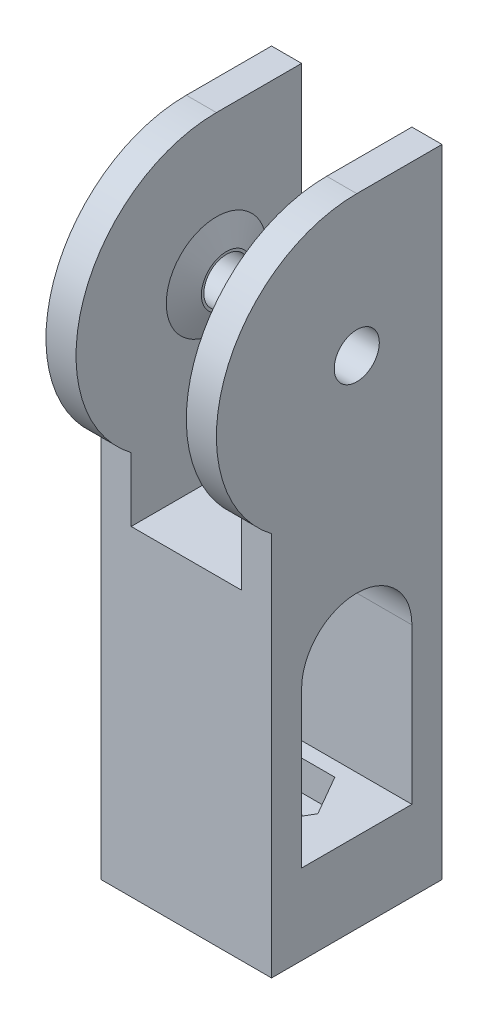
SolidWorks part; units mm, degrees
ref_plane "Front Plane" through (0, 0, 0) normal (0, 0, 1) x (1, 0, 0)
ref_plane "Top Plane" through (0, 0, 0) normal (0, 1, 0) x (1, 0, 0)
ref_plane "Right Plane" through (0, 0, 0) normal (1, 0, 0) x (0, 0, -1)
sketch "Sketch1" plane through (0, 0, 0) normal (0, 0, 1) x (1, 0, 0)
  line L0 (8.5, 32) -> (8.5, 0) construction
  line L1 (0, 0) -> (17, 0)
  line L2 (0, 0) -> (0, 63.5)
  line L3 (0, 63.5) -> (3, 63.5)
  line L4 (17, 0) -> (17, 63.5)
  line L5 (14, 63.5) -> (17, 63.5)
  line L6 (3, 63.5) -> (3, 32)
  line L7 (3, 32) -> (14, 32)
  line L8 (14, 63.5) -> (14, 32)
  dimension "D1" = 63.5
  dimension "D2" = 17
  dimension "D3" = 11
  dimension "D4" = 31.5
extrude "Boss-Extrude1" add sketch "Sketch1" along normal blind 22.5
sketch "Sketch2" plane through (17, 0, 0) normal (1, 0, 0) x (0, 0, -1)
  line L0 (-8.5, 8) -> (-8.5, 0) construction
  line L1 (-14, 23.5) -> (-3, 23.5) construction
  line L2 (-14, 23.5) -> (-14, 8)
  line L3 (-14, 8) -> (-3, 8)
  line L4 (-3, 23.5) -> (-3, 8)
  line L6 (-22.5, 0) -> (0, 0) construction
  line L7 (-8.5, 23.5) -> (-8.5, 49.5) construction
  line L8 (0, 0) -> (0, 63.5) construction
  line L9 (-22.5, 63.5) -> (-8.5, 63.5)
  line L10 (-22.5, 63.5) -> (0, 63.5) construction
  line L11 (-22.5, 63.5) -> (-22.5, 49.5)
  line L12 (-22.5, 0) -> (-22.5, 63.5) construction
  line L13 (-22.5, 0) -> (-22.5, 49.5)
  line L14 (-17, 38.3757) -> (-17, 0)
  line L15 (-22.5, 0) -> (-17, 0)
  arc A0 (-14, 23.5) -> (-3, 23.5) centre (-8.5, 23.5) cw
  circle A1 centre (-8.5, 49.5) radius 4.25 construction
  arc A2 (-8.5, 63.5) -> (-17, 38.3757) centre (-8.5, 49.5) ccw
  point P29 (-17, 19.1879)
  line M9 (0, 63.5) -> (-22.5, 63.5)
  line M10 (-22.5, 63.5) -> (-22.5, 0)
  line M11 (-22.5, 0) -> (0, 0)
  dimension "D3" = 5.5
  dimension "D5" = 8.5
  dimension "D7" = 28
  dimension "D1" = 11
  dimension "D2" = 15.5
  dimension "D4" = 8
  dimension "D6" = 26
  dimension "D8" = 8.5
  dimension "D9" = 5.5
extrude "Cut-Extrude1" cut sketch "Sketch2" against normal through all contours A2 L14 M10 M11 | A2 M9 M10 | A0 L2 L3 L4 | A1 region at (17, 17.9479, 8.5) region at (17, 20.9454, 19.8446) region at (17, 60.3728, 19.3728)
sketch "Sketch3" plane through (0, 0, 0) normal (0, -1, 0) x (1, 0, 0)
  line L0 (0, 0) -> (17, 17) construction
  circle A0 centre (8.5, 8.5) radius 2.3
  dimension "D1" = 4.6
extrude "Cut-Extrude2" cut sketch "Sketch3" against normal up to surface (8 mm away) up to face at (8.5, 8, 8.5)
sketch "Sketch4" plane through (0, 8, 0) normal (0, 1, 0) x (1, 0, 0)
  line L1 (3.8812, -8.5) -> (6.1906, -12.5)
  line L2 (6.1906, -12.5) -> (10.8094, -12.5)
  line L3 (10.8094, -12.5) -> (13.1188, -8.5)
  line L4 (13.1188, -8.5) -> (10.8094, -4.5)
  line L5 (10.8094, -4.5) -> (6.1906, -4.5)
  line L6 (6.1906, -4.5) -> (3.8812, -8.5)
  circle A0 centre (8.5, -8.5) radius 4 construction
  dimension "D1" = 8
extrude "Cut-Extrude3" cut sketch "Sketch4" against normal blind 3
sketch "Sketch5" plane through (14, 0, 0) normal (-1, 0, 0) x (0, 0, 1)
  circle A0 centre (8.5, 49.5) radius 5
  dimension "D1" = 10
ref_plane "Plane1" through (13, 0, 0) normal (-1, 0, 0) x (0, 0, 1)
sketch "Sketch6" plane through (13, 0, 0) normal (-1, 0, 0) x (0, 0, 1)
  circle A0 centre (8.5, 49.5) radius 2.5
  dimension "D1" = 5
loft "Loft1" add profiles "Sketch5", "Sketch6" connector at (14, 44.5, 8.5) connector at (13, 47, 8.5)
ref_plane "Plane2" through (8.5, 0, 0) normal (-1, 0, 0) x (0, 0, 1)
mirror "Mirror1" about plane through (8.5, 0, 0) normal (-1, 0, 0) of "Loft1"
sketch "Sketch7" plane through (17, 0, 0) normal (1, 0, 0) x (0, 0, -1)
  circle A0 centre (-8.5, 49.5) radius 4.25 construction
  dimension "D1" = 8.5
hole_wizard "M4 Clearance Hole1" positions "3DSketch1" profile "Sketch8" hole size "M4" standard "ANSI Metric" end condition through all
sketch3d "3DSketch1"
  point P0 (17, 49.5, 8.5)
sketch "Sketch8" plane through (17, 49.5, 8.5) normal (0, 1, 0) x (0, 0, -1)
  line L0 (0, 0) -> (0, 17)
  line L1 (0, 17) -> (2.25, 17)
  line L2 (2.25, 17) -> (2.25, 0)
  line L5 (2.25, 0) -> (0, 0)
  line L11 (0, -6.35) -> (0, 107.95) construction
  dimension "Thru Hole Dia." = 4.5
  dimension "Thru Hole Depth" = 17
